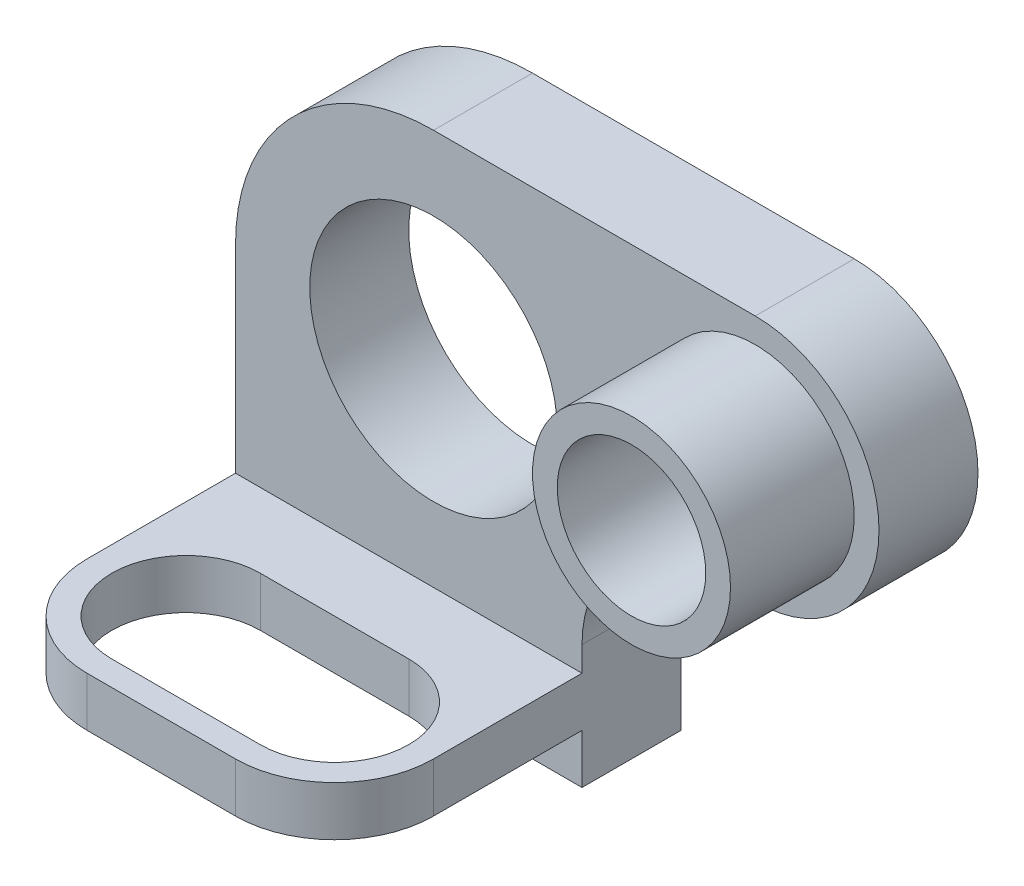
SolidWorks part; units mm, degrees
ref_plane "Front Plane" through (0, 0, 0) normal (0, 0, 1) x (1, 0, 0)
ref_plane "Top Plane" through (0, 0, 0) normal (0, 1, 0) x (1, 0, 0)
ref_plane "Right Plane" through (0, 0, 0) normal (1, 0, 0) x (0, 0, -1)
sketch "Sketch1" plane through (0, 0, 0) normal (0, 0, 1) x (1, 0, 0)
  line L0 (0, 0) -> (0, 60)
  line L1 (40, 100) -> (105, 100)
  line L2 (105, 50) -> (95, 50)
  line L3 (70, 25) -> (70, 0)
  line L4 (70, 0) -> (0, 0)
  line L6 (70, 10) -> (0, 10)
  line L7 (70, 10) -> (70, 20)
  line L8 (70, 20) -> (0, 20)
  line L9 (0, 10) -> (0, 20)
  arc A0 (105, 100) -> (105, 50) centre (105, 75) cw
  circle A1 centre (40, 60) radius 25
  arc A2 (95, 50) -> (70, 25) centre (95, 25) ccw
  arc A3 (0, 60) -> (40, 100) centre (40, 60) cw
  circle A4 centre (105, 75) radius 15
  circle A5 centre (105, 75) radius 20
  point P15 (70, 12.5)
  dimension "D1" = 70
  dimension "D3" = 25
  dimension "D4" = 50
  dimension "D7" = 25
  dimension "D9" = 40
  dimension "D13" = 30
  dimension "D14" = 40
  dimension "D2" = 75
  dimension "D5" = 60
  dimension "D6" = 65
  dimension "D8" = 35
  dimension "D10" = 40
  dimension "D11" = 20
  dimension "D12" = 10
extrude "Boss-Extrude1" add sketch "Sketch1" against normal blind 20 contours A3 L0 L8 L3 A2 L2 A0 L1 A5 A1 | L3 L6 L0 L4 region at (35, 5, 0) region at (1.5264, 40, 0)
extrude "Boss-Extrude2" add sketch "Sketch1<4>" along normal blind 50 and the other way up to surface (20 mm away) contours L3 L8 L0 L6 region at (35, 15, 0) other way up to face at (125, 75, -20)
sketch "Sketch1<4>" plane through (0, 0, 0) normal (0, 0, 1) x (1, 0, 0) same geometry as "Sketch1"
extrude "Boss-Extrude3" add sketch "Sketch1<5>" along normal blind 25 and the other way up to surface (20 mm away) contours A5 A4 region at (85.5657, 75, 0) other way up to face at (125, 75, -20)
sketch "Sketch1<5>" plane through (0, 0, 0) normal (0, 0, 1) x (1, 0, 0) same geometry as "Sketch1"
fillet "Fillet1" radius 20 2 edges at (0, 15, 50) (70, 15, 50)
sketch "Sketch2" plane through (0, 20, 0) normal (0, 1, 0) x (1, 0, 0)
  line L0 (20, -30) -> (50, -30) construction
  line L1 (20, -15) -> (50, -15)
  line L2 (20, -45) -> (50, -45)
  line L3 (0, 0) -> (0, -30) construction
  line L4 (50, -50) -> (20, -50) construction
  arc A0 (20, -15) -> (20, -45) centre (20, -30) ccw
  arc A1 (50, -45) -> (50, -15) centre (50, -30) ccw
  point P2 (35, -30)
  dimension "D3" = 15
  dimension "D1" = 30
  dimension "D2" = 20
  dimension "D4" = 20
extrude "Cut-Extrude1" cut sketch "Sketch2" against normal through all
